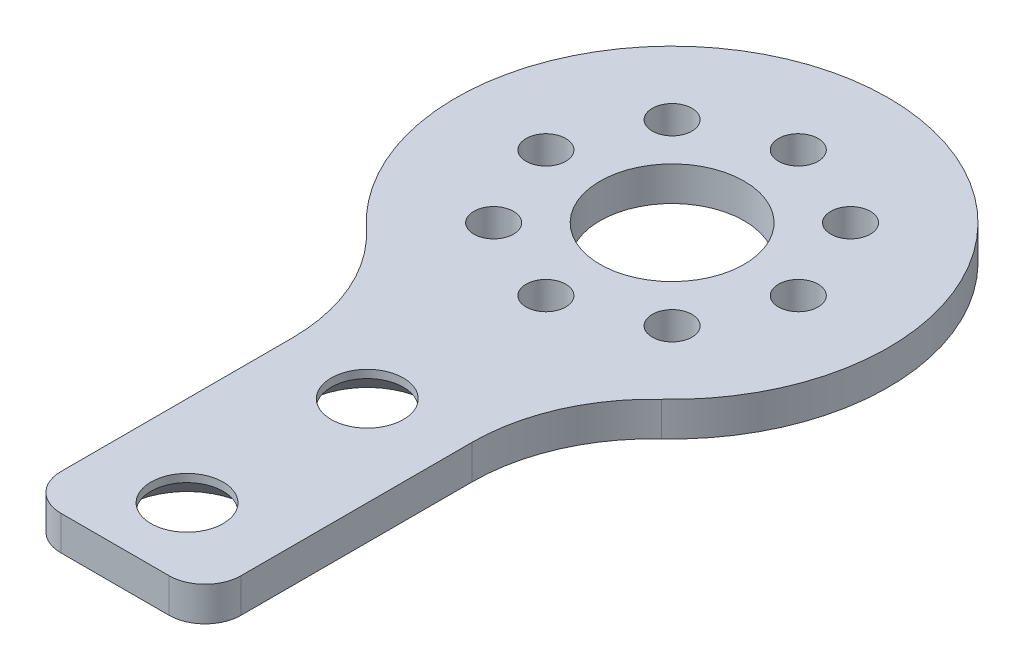
SolidWorks part; units mm, degrees
material "1060 Alloy"
ref_plane "Front Plane" through (0, 0, 0) normal (0, 0, 1) x (1, 0, 0)
ref_plane "Top Plane" through (0, 0, 0) normal (0, 1, 0) x (1, 0, 0)
ref_plane "Right Plane" through (0, 0, 0) normal (1, 0, 0) x (0, 0, -1)
sketch "Sketch1" plane through (0, 0, 0) normal (0, 1, 0) x (1, 0, 0)
  line L0 (-12.5, -77.2718) -> (12.5, -77.2718)
  line L1 (12.5, -77.2718) -> (12.5, -27.2718)
  line L2 (-12.5, -77.2718) -> (-12.5, -27.2718)
  arc A0 (12.5, -27.2718) -> (-12.5, -27.2718) centre (0, 0) ccw
  point P5 (0, -77.2718)
  dimension "D2" = 60
  dimension "D1" = 25
  dimension "D3" = 50
extrude "Boss-Extrude1" add sketch "Sketch1" along normal blind 4.7625 contours A0 L2 L0 L1
sketch "Sketch2" plane through (0, 0, 0) normal (0, -1, 0) x (1, 0, 0)
  circle A0 centre (0, 0) radius 17.5 construction
  point P3 (17.5, 0)
  point P6 (12.3744, -12.3744)
  point P7 (0, -17.5)
  point P8 (-12.3744, -12.3744)
  point P9 (-17.5, 0)
  point P10 (-12.3744, 12.3744)
  point P11 (0, 17.5)
  point P12 (12.3744, 12.3744)
  point P13 (0, 0)
  dimension "D2" = 35
  dimension "D1" = 8
hole_wizard "M5 Clearance Hole1" positions "Sketch3" profile "Sketch4" hole size "M5" standard "ANSI Metric" end condition through all
sketch "Sketch3" plane through (0, 0, 0) normal (0, -1, 0) x (-1, 0, 0)
  point P0 (0, 17.5)
  point P3 (12.3744, 12.3744)
  point P6 (17.5, 0)
  point P9 (12.3744, -12.3744)
  point P12 (0, -17.5)
  point P15 (-12.3744, -12.3744)
  point P18 (-17.5, 0)
  point P21 (-12.3744, 12.3744)
sketch "Sketch4" plane through (0, 0, -17.5) normal (1, 0, 0) x (0, 0, -1)
  line L0 (0, 0) -> (0, 4.7625)
  line L1 (0, 4.7625) -> (2.75, 4.7625)
  line L2 (2.75, 4.7625) -> (2.75, 0.025)
  line L3 (2.75, 0.025) -> (2.775, 0)
  line L5 (2.775, 0) -> (0, 0)
  line L6 (-2.75, 0.025) -> (-2.775, 0) construction
  line L11 (0, -6.35) -> (0, 107.95) construction
  dimension "Thru Hole Dia." = 5.5
  dimension "Thru Hole Depth" = 4.7625
  dimension "Near C'Sink Dia." = 5.55
  dimension "Near C'Sink Angle" = 90
sketch "Sketch5" plane through (0, 0, 0) normal (0, -1, 0) x (1, 0, 0)
  circle A0 centre (0, 0) radius 10
  dimension "D1" = 20
extrude "Cut-Extrude1" cut sketch "Sketch5" against normal through all
sketch "Sketch6" plane through (0, 0, 0) normal (0, -1, 0) x (1, 0, 0)
  line L0 (0, 77.2718) -> (0, 42.2718) construction
  line L1 (-12.5, 77.2718) -> (12.5, 77.2718) construction
  point P5 (0, 67.2718)
  dimension "D1" = 25
  dimension "D2" = 10
hole_wizard "CSK for M8 Flat Head Machine Screw1" positions "Sketch7" profile "Sketch8" countersink size "M8" standard "ANSI Metric" end condition through all
sketch "Sketch7" plane through (0, 0, 0) normal (0, -1, 0) x (-1, 0, 0)
  point P0 (0, -42.2718)
  point P3 (0, -67.2718)
sketch "Sketch8" plane through (0, 0, 42.2718) normal (1, 0, 0) x (0, 0, -1)
  line L0 (0, 0) -> (0, 4.7625)
  line L1 (0, 4.7625) -> (5, 4.7625)
  line L2 (5, 4.7625) -> (5, 3.65)
  line L3 (5, 3.65) -> (8.65, 0)
  line L5 (8.65, 0) -> (0, 0)
  line L6 (-5, 3.65) -> (-8.65, 0) construction
  line L11 (0, -6.35) -> (0, 107.95) construction
  dimension "Thru Hole Dia." = 10
  dimension "Thru Hole Depth" = 4.7625
  dimension "Near C'Sink Dia." = 17.3
  dimension "Near C'Sink Angle" = 90
fillet "Fillet1" radius 25 2 edges at (-12.5, 2.3813, 27.2718) (12.5, 2.3813, 27.2718)
fillet "Fillet2" radius 5 2 edges at (12.5, 2.3813, 77.2718) (-12.5, 2.3813, 77.2718)
